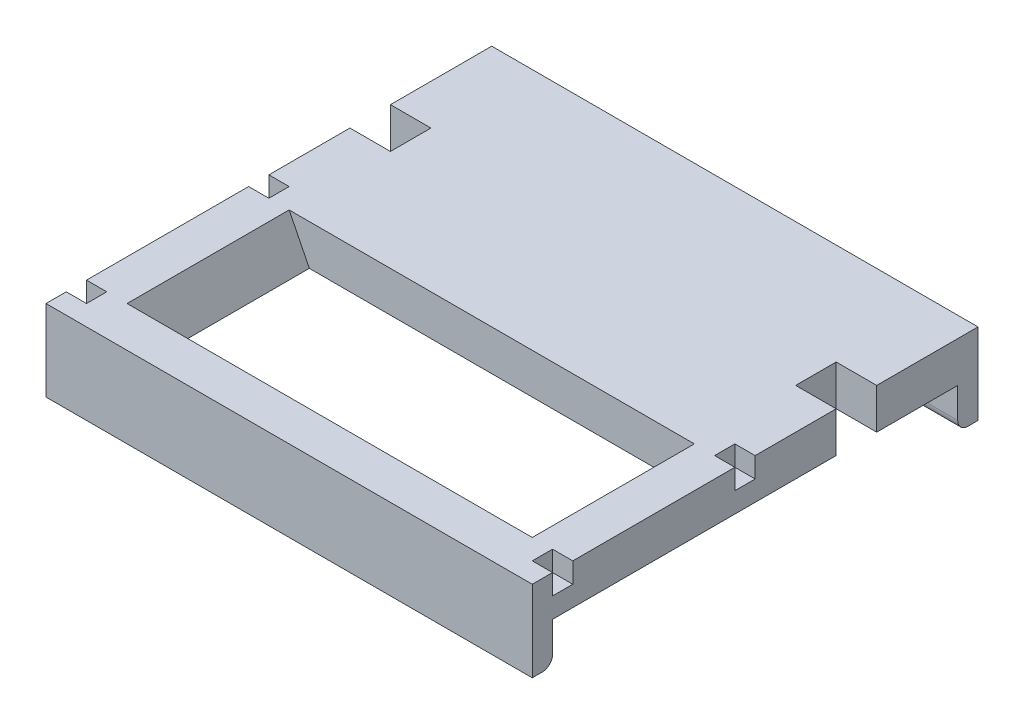
SolidWorks part; units mm, degrees
ref_plane "Front Plane" through (0, 0, 0) normal (0, 0, 1) x (1, 0, 0)
ref_plane "Top Plane" through (0, 0, 0) normal (0, 1, 0) x (1, 0, 0)
ref_plane "Right Plane" through (0, 0, 0) normal (1, 0, 0) x (0, 0, -1)
sketch "Sketch1" plane through (0, 0, 0) normal (0, 1, 0) x (1, 0, 0)
  line L0 (0, 50) -> (0, 32.1573)
  line L1 (-60, 50) -> (60, 50)
  line L2 (-60, 50) -> (-60, -50)
  line L3 (-60, -50) -> (60, -50)
  line L4 (60, 50) -> (60, -50)
  line L5 (-60, 50) -> (-60, 0)
  line L6 (-60, 25) -> (-50, 25)
  line L7 (-60, 50) -> (-60, 40)
  line L8 (-58, 28) -> (-52, 28)
  line L9 (-58, 28) -> (-58, 22)
  line L10 (-58, 22) -> (-52, 22)
  line L11 (-52, 28) -> (-52, 22)
  line L12 (-58, 28) -> (-52, 22) construction
  line L13 (-58, 22) -> (-52, 28) construction
  line L14 (-60, 45) -> (-50, 45)
  line L15 (-60, 0) -> (-60, 10)
  line L16 (-60, 5) -> (-50, 5)
  line L17 (-60, 5) -> (-60, 2)
  line L18 (-58, 2) -> (-52, 2)
  line L19 (-60, 45) -> (-60, 48)
  line L20 (-58, 8) -> (-52, 8)
  line L21 (-58, 8) -> (-58, 2)
  line L22 (-58, 2) -> (-52, 2)
  line L23 (-52, 8) -> (-52, 2)
  line L24 (-58, 8) -> (-52, 2) construction
  line L25 (-58, 2) -> (-52, 8) construction
  line L26 (58, 22) -> (52, 22)
  line L27 (-52, 42) -> (-58, 42)
  line L28 (-52, 42) -> (-52, 48)
  line L29 (-52, 48) -> (-58, 48)
  line L30 (-58, 42) -> (-58, 48)
  line L31 (-52, 42) -> (-58, 48) construction
  line L32 (-52, 48) -> (-58, 42) construction
  line L33 (58, 2) -> (52, 2)
  line L34 (52, 8) -> (52, 2)
  line L35 (58, 8) -> (52, 8)
  line L36 (58, 8) -> (58, 2)
  line L37 (52, 48) -> (58, 48)
  line L38 (52, 42) -> (52, 48)
  line L39 (52, 42) -> (58, 42)
  line L40 (58, 42) -> (58, 48)
  line L41 (-60, 0) -> (-60, -5)
  line L42 (52, 28) -> (52, 22)
  line L43 (-60, -2.5) -> (-60, -1)
  line L44 (58, 28) -> (52, 28)
  line L45 (58, 28) -> (58, 22)
  line L46 (-60, -2.5) -> (-57.5, -2.5)
  line L47 (-60, -50) -> (-60, 0)
  line L48 (-59, -4) -> (-56, -4)
  line L49 (-59, -4) -> (-59, -1)
  line L50 (-59, -1) -> (-56, -1)
  line L51 (-56, -4) -> (-56, -1)
  line L52 (-60, -50) -> (-60, 0)
  line L53 (-55, -5) -> (-60, -5)
  line L54 (-55, -5) -> (-55, 0)
  line L55 (-59, -49) -> (-56, -49)
  line L56 (-56, -46) -> (-56, -49)
  line L57 (-59, -46) -> (-56, -46)
  line L58 (-59, -46) -> (-59, -49)
  line L59 (-55, 0) -> (-60, 0)
  line L60 (59, -46) -> (59, -49)
  line L61 (59, -46) -> (56, -46)
  line L62 (56, -46) -> (56, -49)
  line L63 (59, -49) -> (56, -49)
  line L64 (59, -1) -> (56, -1)
  line L65 (56, -4) -> (56, -1)
  line L66 (59, -4) -> (56, -4)
  line L67 (59, -4) -> (59, -1)
  line L68 (-50, 50) -> (-50, -50)
  line L69 (50, 50) -> (50, -50)
  line L70 (-60, -5) -> (-60, 0)
  line L71 (-55, -5) -> (-60, 0) construction
  line L72 (-55, 0) -> (-60, -5) construction
  line L73 (-60, -50) -> (-60, -23.4585)
  line L74 (-60, 0) -> (-60, -50)
  line L75 (-60, -50) -> (-60, -47.5)
  line L76 (0, -50) -> (0, -45)
  line L77 (-55, -45) -> (-60, -45)
  line L78 (-55, -45) -> (-55, -50)
  line L79 (-55, -50) -> (-60, -50)
  line L80 (-60, -45) -> (-60, -50)
  line L81 (-55, -45) -> (-60, -50) construction
  line L82 (-55, -50) -> (-60, -45) construction
  line L83 (55, -50) -> (60, -50)
  line L84 (60, -45) -> (60, -50)
  line L85 (55, -45) -> (60, -45)
  line L86 (55, -45) -> (55, -50)
  line L87 (55, 0) -> (60, 0)
  line L88 (60, -5) -> (60, 0)
  line L89 (55, -5) -> (60, -5)
  line L90 (55, -5) -> (55, 0)
  line L91 (-60, 25) -> (-60, 20)
  line L92 (-60, 20) -> (-55, 20)
  line L93 (50, 20) -> (60, 20)
  line L94 (-50, 30) -> (-60, 30)
  line L95 (-50, 30) -> (-50, 20)
  line L96 (-50, 20) -> (-60, 20)
  line L97 (-60, 30) -> (-60, 20)
  line L98 (-50, 30) -> (-60, 20) construction
  line L99 (-50, 20) -> (-60, 30) construction
  line L100 (60, 30) -> (60, 20)
  line L101 (50, 30) -> (60, 30)
  line L102 (50, 30) -> (50, 20)
  line L103 (52, 48) -> (58, 48)
  line L104 (58, 42) -> (58, 48)
  line L105 (52, 42) -> (52, 48)
  line L106 (52, 42) -> (58, 42)
  line L107 (52, 28) -> (58, 28)
  line L108 (58, 22) -> (58, 28)
  line L109 (52, 22) -> (52, 28)
  line L110 (58, 22) -> (52, 22)
  point P0 (0, 0)
  point P10 (-55, 25)
  point P21 (-55, 5)
  point P24 (-55, 45)
  point P49 (-57.5, -47.5)
  point P51 (-57.5, -2.5)
  point P90 (-55, 25)
  dimension "D1" = 120
  dimension "D2" = 100
  dimension "D3" = 6
  dimension "D4" = 6
  dimension "D5" = 6
extrude "Boss-Extrude1" add sketch "Sketch1" against normal blind 10 contours L69 L1 L68 L3 | L1 L69 L3 L4 L60 L63 L62 L61 L35 L36 L33 L34 L40 L39 L38 L37 L67 L66 L65 L64 | L36 L35 L34 L33 | L66 L67 L64 L65 | L63 L60 L61 L62 | L68 L16 L23 L18 L21 L15 L2 L41 L3 L58 L57 L56 L55 L51 L48 L49 L50 | L57 L58 L55 L56 | L48 L51 L50 L49 | L68 L6 L11 L10 L9 L5 L2 L16 L21 L20 L23 | L23 L20 L21 L16 | L23 L16 L21 L18 | L11 L6 L9 L10 | L11 L8 L9 L6 | L68 L14 L28 L27 L30 L7 L5 L6 L9 L8 L11 | L68 L1 L2 L7 L14 L30 L29 L28 | L30 L14 L28 L29 | L30 L27 L28 L14 | L96 L68 L6 L11 L10 L9 L5 L92 | L68 L94 L2 L6 L9 L8 L11 | L54 L59 L2 L41 L49 L50 L51 L48 L53 | L78 L77 L74 L3 L58 L57 L56 L55 | L85 L86 L3 L4 L60 L63 L62 L61 | L90 L89 L4 L87 L67 L66 L65 L64 | L45 L44 L42 L26 | L39 L40 L37 L38 | L69 L101 L4 L1 L40 L39 L38 L37 | L101 L69 L93 L4 L44 L45 L26 L42 | L26 L42 L44 L45 | L95 L94 L97 L96 | L9 L8 L11 L10 | L54 L53 L70 L59 | L78 L77 L80 L79 | L84 L85 L86 L83 | L87 L88 L89 L90 | L2 L1 L4 L3 | L38 L37 L40 L39 region at (-55, 0, -48.0625) region at (0, 0, 0) region at (-55, 0, -36.6818) region at (55, 0, -38.9024) region at (-55, 0, -43.5) region at (-55, 0, -46.5) region at (-55, 0, -28.0625) region at (55, 0, -29.8586) region at (-55, 0, -21.9375) region at (54.7964, 0, 15.3583) region at (-55, 0, -23.5) region at (-55, 0, -26.5) region at (-55, 0, -13.3182) region at (-54.7407, 0, 23.2116) region at (59.9293, 0, 2.5) region at (55.0707, 0, 47.5) region at (-55, 0, -3.5) region at (-55, 0, -6.5) region at (-57.5, 0, 49.9293) region at (-58.9576, 0, 1.75) region at (-57.5, 0, 0.0707) region at (55, 0, -25) region at (55, 0, -5) region at (55, 0, -45) region at (-57.5, 0, 47.5) region at (57.5, 0, 47.5) region at (57.5, 0, 2.5)
sketch "Sketch2" plane through (0, -10, 0) normal (0, -1, 0) x (1, 0, 0)
  line L0 (-50, 50) -> (50, 50)
  line L1 (50, 50) -> (50, -50)
  line L2 (50, -50) -> (-50, -50)
  line L3 (-50, -50) -> (-50, 50)
  line L4 (-50, 50) -> (-50, 45)
  line L5 (-50, 45) -> (-45, 45)
  line L6 (-45, 45) -> (-45, 50)
  line L7 (-45, 50) -> (-50, 50)
  line L8 (-50, 50) -> (-50, 47.5)
  line L9 (-50, 50) -> (-47.5, 50)
  line L10 (-50, 47.5) -> (-47.5, 47.5)
  line L11 (-47.5, 47.5) -> (-47.5, 49)
  line L12 (-47.5, 47.5) -> (-46, 47.5)
  line L13 (-50, -5) -> (-45, -5)
  line L14 (-49, 46) -> (-46, 46)
  line L15 (-49, 46) -> (-49, 49)
  line L16 (-49, 49) -> (-46, 49)
  line L17 (-46, 46) -> (-46, 49)
  line L18 (-49, 46) -> (-46, 49) construction
  line L19 (-49, 49) -> (-46, 46) construction
  line L20 (-50, 0) -> (-40, 0)
  line L21 (-40, 0) -> (-40, -10)
  line L22 (-40, -10) -> (-50, -10)
  line L23 (-50, -10) -> (-50, 0)
  line L24 (-45, -5) -> (-45, -2)
  line L25 (-45, -5) -> (-42, -5)
  line L26 (0, -50) -> (0, -29.8037)
  line L27 (-48, -8) -> (-42, -8)
  line L28 (-48, -8) -> (-48, -2)
  line L29 (-48, -2) -> (-42, -2)
  line L30 (-42, -8) -> (-42, -2)
  line L31 (-48, -8) -> (-42, -2) construction
  line L32 (-48, -2) -> (-42, -8) construction
  line L33 (-50, -25) -> (-32.9312, -25)
  line L34 (-48, -48) -> (-42, -48)
  line L35 (-42, -42) -> (-42, -48)
  line L36 (-48, -42) -> (-42, -42)
  line L37 (-48, -42) -> (-48, -48)
  line L38 (48, -42) -> (48, -48)
  line L39 (48, -42) -> (42, -42)
  line L40 (42, -42) -> (42, -48)
  line L41 (48, -48) -> (42, -48)
  line L42 (48, -2) -> (42, -2)
  line L43 (42, -8) -> (42, -2)
  line L44 (48, -8) -> (42, -8)
  line L45 (48, -8) -> (48, -2)
  line L46 (49, 49) -> (46, 49)
  line L47 (46, 46) -> (46, 49)
  line L48 (49, 46) -> (46, 46)
  line L49 (49, 46) -> (49, 49)
  line L50 (50, 50) -> (50, 0)
  line L51 (50, 0) -> (50, 25)
  line L52 (50, 25) -> (29.5204, 25)
  line L53 (-49, 1) -> (-46, 1)
  line L54 (-46, 4) -> (-46, 1)
  line L55 (-49, 4) -> (-46, 4)
  line L56 (-49, 4) -> (-49, 1)
  line L57 (49, 4) -> (49, 1)
  line L58 (49, 4) -> (46, 4)
  line L59 (46, 4) -> (46, 1)
  line L60 (49, 1) -> (46, 1)
  line L61 (-50, -5) -> (-50, -25)
  line L62 (-50, -15) -> (-38.6156, -15)
  line L63 (-48, -28) -> (-42, -28)
  line L64 (-42, -22) -> (-42, -28)
  line L65 (-48, -22) -> (-42, -22)
  line L66 (-48, -22) -> (-48, -28)
  line L67 (48, -22) -> (48, -28)
  line L68 (48, -22) -> (42, -22)
  line L69 (42, -22) -> (42, -28)
  line L70 (48, -28) -> (42, -28)
  line L71 (-45, 5) -> (-40, 5)
  line L72 (45, 5) -> (-45, 5)
  line L73 (45, 5) -> (45, 45)
  line L74 (45, 45) -> (-45, 45)
  line L75 (-45, 5) -> (-45, 45)
  line L76 (45, 5) -> (-45, 45) construction
  line L77 (45, 45) -> (-45, 5) construction
  point P78 (0, 25)
  dimension "D1" = 6
extrude "Cut-Extrude1" cut sketch "Sketch2" against normal blind 10 contours L75 L72 L73 L74 region at (0, -10, 25)
extrude "Cut-Extrude2" cut sketch "Sketch2<3>" against normal blind 6 contours L48 L49 L46 L47 | L55 L56 L53 L54 | L60 L57 L58 L59 | L70 L67 L68 L69 | L14 L17 L16 L15 | L63 L64 L65 L66 region at (47.5, -10, 47.5) region at (-47.5, -10, 2.5) region at (47.5, -10, 2.5) region at (45, -10, -25)
sketch "Sketch2<3>" plane through (0, -10, 0) normal (0, -1, 0) x (1, 0, 0) same geometry as "Sketch2"
sketch "Sketch3" plane through (0, 0, 0) normal (0, 1, 0) x (1, 0, 0)
  line L0 (-50, -5) -> (-50, -45)
  line L1 (50, -5) -> (50, -45)
  line L2 (-60, -5) -> (-50, -5)
  line L3 (-50, -45) -> (-60, -45)
  line L4 (-60, 50) -> (-60, -50) construction
  line L5 (50, -45) -> (60, -45)
  line L6 (60, 50) -> (60, -50) construction
  line L7 (50, -5) -> (60, -5)
  line L8 (-50, -5) -> (-45, -5)
  line L9 (-45, -5) -> (-45, -45)
  line L10 (-45, -45) -> (-50, -45)
  line L11 (45, -5) -> (45, -45)
  line L12 (45, -45) -> (50, -45)
  line L13 (45, -5) -> (50, -5)
chamfer "Chamfer2" distance 5 angle 63.5 1 edges at (-45, 0, 25) first distance on face at (0, 0, 0)
chamfer "Chamfer3" distance 10 angle 26.565 1 edges at (45, 0, 25) first distance on face at (45, -5, 25)
extrude "Cut-Extrude3" cut sketch "Sketch1<6>" against normal blind 10 contours L68 L94 L2 L6 L9 L8 L11 | L11 L8 L9 L6 | L11 L6 L9 L10 | L96 L68 L6 L11 L10 L9 L5 L92 | L45 L44 L42 L26 | L101 L69 L93 L4 L44 L45 L26 L42 region at (-55, 0, -28.0625) region at (55, 0, -29.8586) region at (-55, 0, -21.9375) region at (-55, 0, -23.5) region at (-55, 0, -26.5) region at (55, 0, -25)
sketch "Sketch1<6>" plane through (0, 0, 0) normal (0, 1, 0) x (1, 0, 0) same geometry as "Sketch1"
extrude "Cut-Extrude4" cut sketch "Sketch1<7>" against normal blind 5 contours L66 L67 L64 L65 | L90 L89 L4 L87 L67 L66 L65 L64 | L63 L60 L61 L62 | L85 L86 L3 L4 L60 L63 L62 L61 | L57 L58 L55 L56 | L78 L77 L74 L3 L58 L57 L56 L55 | L48 L51 L50 L49 | L54 L59 L2 L41 L49 L50 L51 L48 L53 region at (59.9293, 0, 2.5) region at (55.0707, 0, 47.5) region at (-57.5, 0, 49.9293) region at (-58.9576, 0, 1.75) region at (-57.5, 0, 0.0707) region at (-57.5, 0, 47.5) region at (57.5, 0, 47.5) region at (57.5, 0, 2.5)
sketch "Sketch1<7>" plane through (0, 0, 0) normal (0, 1, 0) x (1, 0, 0) same geometry as "Sketch1"
sketch "Sketch5" plane through (0, 0, 0) normal (0, 1, 0) x (1, 0, 0)
  line L0 (-60, -50) -> (60, -50)
  line L1 (60, -50) -> (60, -55)
  line L2 (60, -55) -> (-60, -55)
  line L3 (-60, -55) -> (-60, -50)
  line L4 (-60, 50) -> (60, 50)
  line L5 (60, 50) -> (60, 55)
  line L6 (60, 55) -> (-60, 55)
  line L7 (-60, 55) -> (-60, 50)
extrude "Boss-Extrude3" add sketch "Sketch5" against normal blind 20
fillet "Fillet2" radius 2.5 2 edges at (0, -20, 50) (0, -20, -50)
